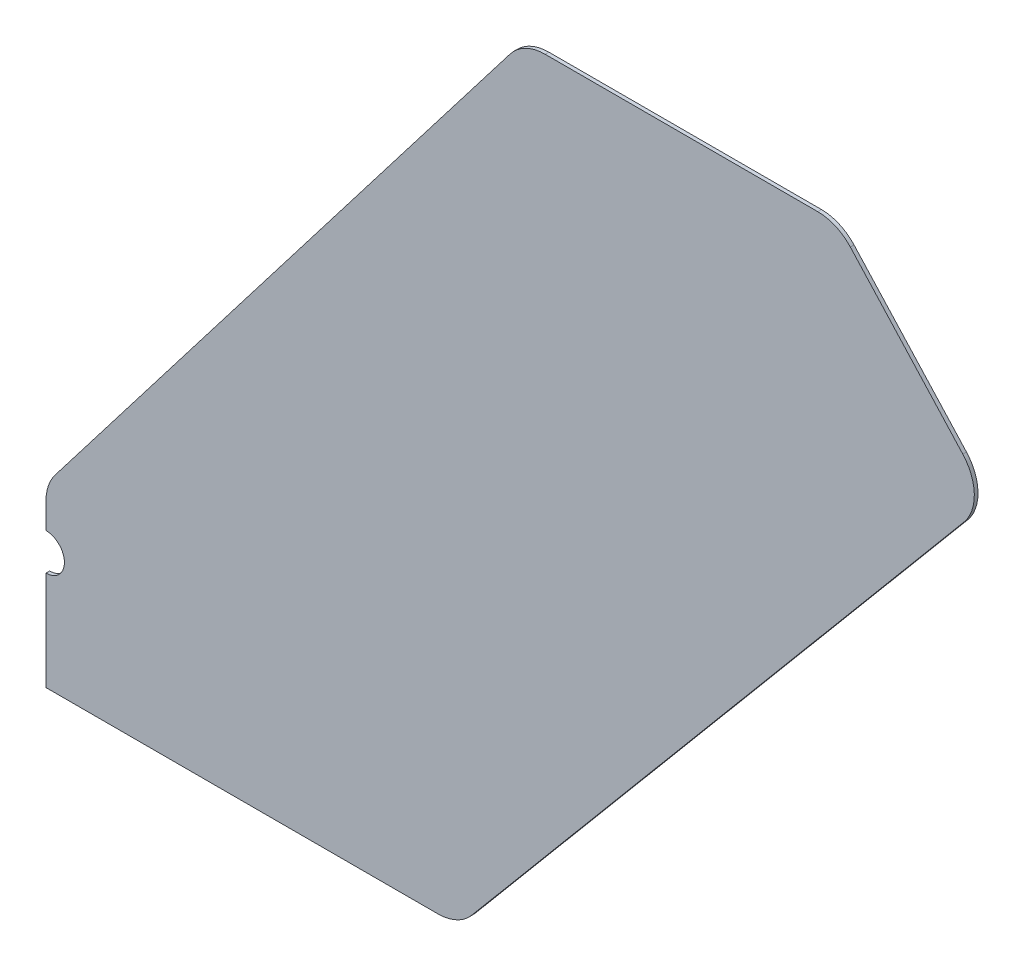
SolidWorks part; units mm, degrees
ref_plane "Front Plane" through (0, 0, 0) normal (0, 0, 1) x (1, 0, 0)
ref_plane "Top Plane" through (0, 0, 0) normal (0, 1, 0) x (1, 0, 0)
ref_plane "Right Plane" through (0, 0, 0) normal (1, 0, 0) x (0, 0, -1)
sketch "Sketch1" plane through (0, 0, 0) normal (0, 0, 1) x (1, 0, 0)
  line L0 (-134.197, 0) -> (131.8138, 0)
  line L1 (-134.197, 0) -> (-134.197, 67.3047)
  line L2 (-127.9849, 128.0841) -> (180.8425, 529.9745)
  line L3 (154.7951, 10.7164) -> (488.8828, 408.8666)
  line L4 (204.6303, 541.695) -> (389.6171, 541.695)
  line L6 (488.0555, 448.3789) -> (411.7711, 531.9238)
  line L7 (-134.197, 92.3047) -> (-134.197, 109.8047)
  arc A0 (131.8138, 0) -> (154.7951, 10.7164) centre (131.8138, 30) ccw
  arc A1 (-134.197, 109.8047) -> (-127.9849, 128.0841) centre (-104.197, 109.8047) cw
  arc A2 (180.8425, 529.9745) -> (204.6303, 541.695) centre (204.6303, 511.695) cw
  arc A3 (389.6171, 541.695) -> (411.7711, 531.9238) centre (389.6171, 511.695) cw
  arc A4 (488.8828, 408.8666) -> (488.0555, 448.3789) centre (465.9015, 428.1502) ccw
  arc A5 (-134.197, 67.3047) -> (-134.197, 92.3047) centre (-134.197, 79.8047) ccw
  point P3 (-134.197, 79.8047)
  point P10 (145.803, 0)
  point P13 (-134.197, 120)
  point P16 (189.849, 541.695)
  point P20 (402.849, 541.695)
  point P23 (505.764, 428.9849)
  dimension "D6" = 30
  dimension "D9" = 30
  dimension "D10" = 30
  dimension "D12" = 25
  dimension "D1" = 280
  dimension "D2" = 120
  dimension "D3" = 531.82
  dimension "D4" = 142.46
  dimension "D5" = 130
  dimension "D7" = 560
  dimension "D8" = 213
  dimension "D11" = 30
base flange "Base-Flange1" sketch "Sketch1" thickness 2.5 reverse thickness direction no parameters "D1"=0.7366
sketch "Bend-Lines1" [suppressed] plane through (0, 0, 0) normal (0, 1, 0) x (1, 0, 0)
sketch "Bounding-Box1" [suppressed] plane through (0, 0, 0) normal (0, 1, 0) x (1, 0, 0)
sheet metal parameters "Sheet-Metal1" thickness 2.5 parameters "D1"=0.7366
flat pattern "Flat-Pattern1" [suppressed]
sketch "Bend-Lines2" plane through (0, 0, 0) normal (0, 1, 0) x (1, 0, 0)
sketch3d "Bounding-Box2" [suppressed]
  line L0 (164.3107, -217.6778, 0) -> (651.9824, 363.5066, 0) construction
  line L1 (-76.1099, -15.9409, 0) -> (411.5617, 565.2435, 0) construction
  line L2 (164.3107, -217.6778, 0) -> (-76.1099, -15.9409, 0) construction
  line L3 (651.9824, 363.5066, 0) -> (411.5617, 565.2435, 0) construction
